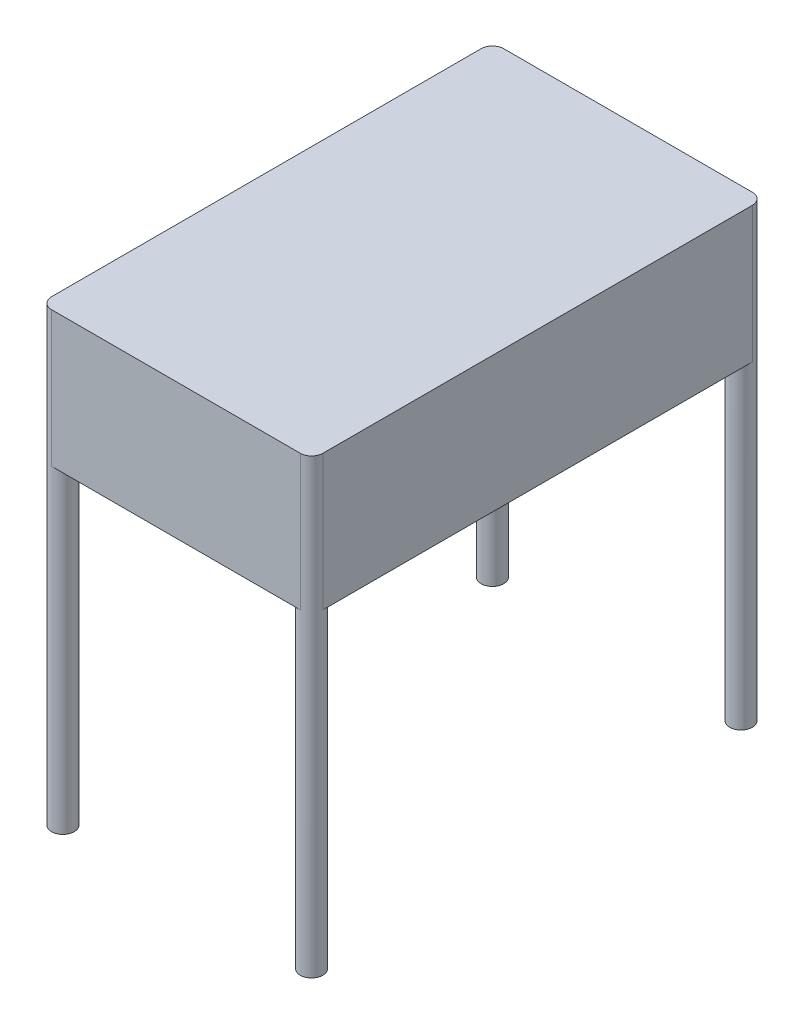
SolidWorks part; units mm, degrees
material "红木"
ref_plane "前视基准面" through (0, 0, 0) normal (0, 0, 1) x (1, 0, 0)
ref_plane "上视基准面" through (0, 0, 0) normal (0, 1, 0) x (1, 0, 0)
ref_plane "右视基准面" through (0, 0, 0) normal (1, 0, 0) x (0, 0, -1)
sketch "草图2" plane through (0, 0, 0) normal (0, 1, 0) x (1, 0, 0)
  line L1 (-300, -500) -> (300, -500)
  line L2 (-300, -500) -> (-300, 500)
  line L3 (-300, 500) -> (300, 500)
  line L4 (300, -500) -> (300, 500)
  line L5 (-300, -500) -> (300, 500) construction
  line L6 (-300, 500) -> (300, -500) construction
  point P0 (0, 0)
  dimension "D1" = 1000
  dimension "D2" = 600
extrude "凸台-拉伸1" add sketch "草图2" against normal blind 300
fillet "圆角1" radius 25 4 edges at (-300, -150, -500) (300, -150, -500) (-300, -150, 500) (300, -150, 500)
sketch "草图3" plane through (0, 0, 0) normal (0, 1, 0) x (1, 0, 0)
  circle A0 centre (275, -475) radius 25
  arc A1 (275, -500) -> (300, -475) centre (275, -475) ccw construction
extrude "凸台-拉伸2" add sketch "草图3" against normal blind 1000
mirror "镜向1" about plane through (0, 0, 0) normal (1, 0, 0) of "凸台-拉伸2"
mirror "镜向2" about plane through (0, 0, 0) normal (0, 0, 1) of "镜向1", "凸台-拉伸2"
